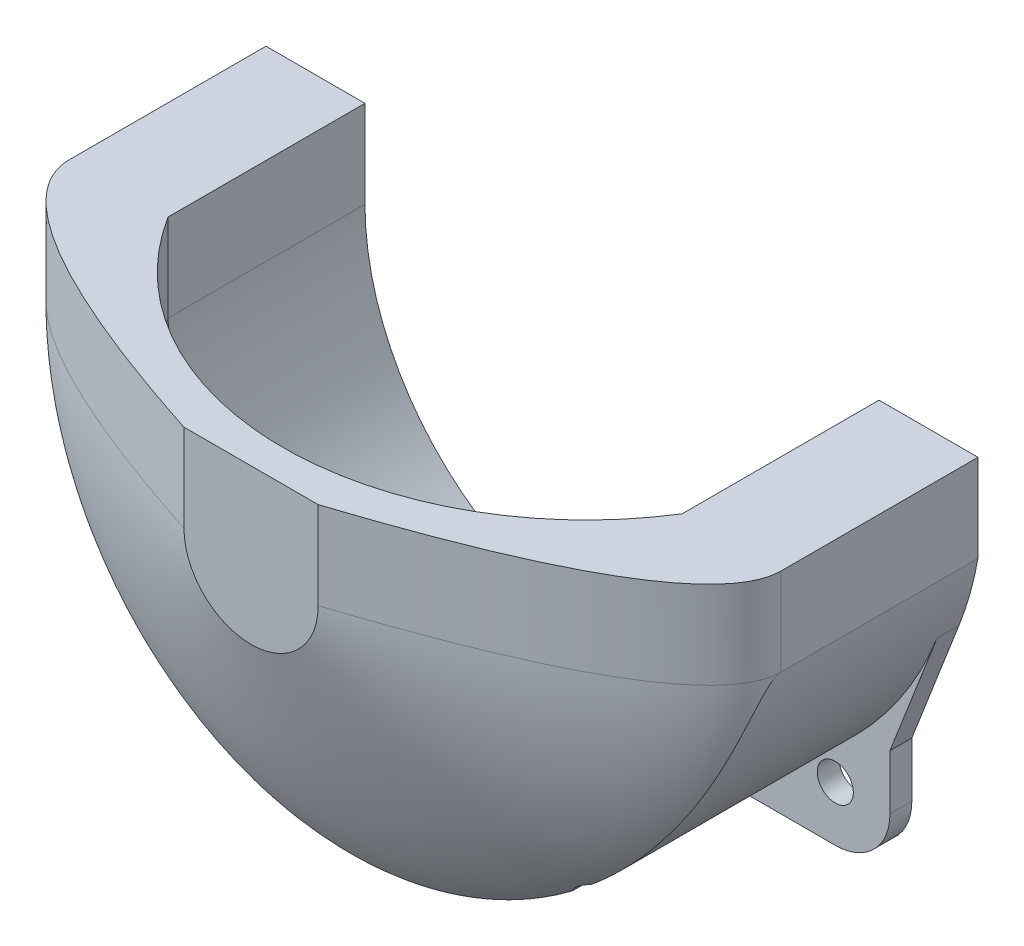
SolidWorks part; units mm, degrees
ref_plane "前视基准面" through (0, 0, 0) normal (0, 0, 1) x (1, 0, 0)
ref_plane "上视基准面" through (0, 0, 0) normal (0, 1, 0) x (1, 0, 0)
ref_plane "右视基准面" through (0, 0, 0) normal (1, 0, 0) x (0, 0, -1)
sketch "草图1" plane through (0, 0, 0) normal (0, 0, 1) x (1, 0, 0)
  line L0 (-1000, 0) -> (49000, 0)
  line L1 (-26.5, 27.25) -> (26.5, 27.25)
  line L2 (-26.5, 27.25) -> (-26.5, -27.25)
  line L3 (-26.5, -27.25) -> (26.5, -27.25)
  line L4 (26.5, 27.25) -> (26.5, -27.25)
  line L5 (-26.5, 27.25) -> (26.5, -27.25) construction
  line L6 (-26.5, -27.25) -> (26.5, 27.25) construction
  circle A0 centre (0, 0) radius 23.5
  dimension "D1" = 47
  dimension "D2" = 27.25
  dimension "D3" = 53
extrude "凸台-拉伸1" add sketch "草图1" along normal blind 2 contours A0 L0 L2 L3 L4 region at (-25, -0.5959, 0)
fillet "圆角1" radius 5 2 edges at (-26.5, -27.25, 1) (26.5, -27.25, 1)
sketch "草图2" plane through (0, 0, 2) normal (0, 0, 1) x (1, 0, 0)
  line L0 (42.3459, 23.4354) -> (26.5, -17.25) construction
  line L1 (-26.5, -17.25) -> (-42.3459, 23.4354) construction
  line L2 (33.2184, 0) -> (26.5, -17.25)
  line L3 (-26.5, -17.25) -> (-33.2184, 0)
  line L4 (-26.5, 0) -> (-33.2184, 0)
  line L5 (26.5, 0) -> (33.2184, 0)
  line L11 (-26.5, 0) -> (-26.5, -22.25)
  line L12 (-21.5, -27.25) -> (21.5, -27.25)
  line L13 (26.5, -22.25) -> (26.5, 0)
  line L14 (26.5, 0) -> (23.5, 0)
  line L15 (-23.5, 0) -> (-26.5, 0)
  line L16 (-26.5, 0) -> (-26.5, -17.25)
  line L18 (26.5, -17.25) -> (26.5, 0)
  circle A0 centre (-21.5, -22.25) radius 1.65 construction
  circle A1 centre (21.5, -22.25) radius 1.65 construction
  circle A2 centre (-21.5, -22.25) radius 1.65
  circle A3 centre (21.5, -22.25) radius 1.65
  arc A7 (-26.5, -22.25) -> (-21.5, -27.25) centre (-21.5, -22.25) ccw
  arc A8 (21.5, -27.25) -> (26.5, -22.25) centre (21.5, -22.25) ccw
  arc A9 (-23.5, 0) -> (23.5, 0) centre (0, 0) ccw
  dimension "D1" = 0
extrude "凸台-拉伸2" add sketch "草图2" against normal blind 2
extrude "切除-拉伸1" cut sketch "草图2<2>" against normal blind 2 contours A2 | A3 region at (-21.5, -22.25, 2) region at (21.5, -22.25, 2)
sketch "草图2<2>" plane through (0, 0, 2) normal (0, 0, 1) x (1, 0, 0) same geometry as "草图2"
sketch "草图5" plane through (0, 0, 2) normal (0, 0, 1) x (1, 0, 0)
  line L0 (-33.2184, 0) -> (-26.5, -17.25) construction
  line L1 (26.5, -17.25) -> (33.2184, 0) construction
  line L2 (-21.5, -27.25) -> (21.5, -27.25) construction
  line L3 (23.5, 0) -> (33.2184, 0) construction
  line L4 (-33.2184, 0) -> (-23.5, 0) construction
  line L5 (23.5, 0) -> (32.5483, 0)
  line L6 (-32.5483, 0) -> (-23.5, 0)
  arc A0 (-32.5483, 0) -> (32.5483, 0) centre (0, 5.8134) ccw
  arc A1 (-23.5, 0) -> (23.5, 0) centre (0, 0) ccw construction
  arc A2 (-23.5, 0) -> (23.5, 0) centre (0, 0) ccw
extrude "凸台-拉伸3" add sketch "草图5" along normal blind 8
ref_plane "基准面4" through (0, 0, 0) normal (0, 1, 0) x (1, 0, 0)
sketch "草图8" plane through (0, 0, 0) normal (0, 1, 0) x (1, 0, 0)
  line L0 (0, -1000) -> (0, 49000) construction
  line L1 (0, -10) -> (23.5, -19) construction
  line L2 (-23.5, -10) -> (23.5, -10) construction
  line L3 (23.5, -10) -> (23.5, 0) construction
  line L4 (32.5483, -10) -> (23.5, -10) construction
  line L5 (32.5483, -10) -> (32.5483, -2) construction
  line L6 (32.5483, -10) -> (23.5, -10)
  line L7 (0, -28) -> (0, -23)
  arc A1 (0, -23) -> (23.5, -10) centre (0, 4.7404) ccw
  spline S1 degree 3 poles (32.5483, -10) (32.5483, -19.5795) (-2.0955, -28) (0, -28) knots 0 0 0 0 1 1 1 1
  dimension "D3" = 9
  dimension "D1" = 5
  dimension "D2" = 13
revolve "旋转4" add sketch "草图8" angle 180 about L7 region at (17.7639, 0, 18.2957)
sketch "草图11" plane through (0, 0, 10) normal (0, 0, -1) x (-1, 0, 0)
  line L0 (-23.5, 0) -> (-22.7697, 0)
  line L1 (22.7697, 0) -> (23.5, 0)
  line L12 (-33.2184, 0) -> (-30.8092, -6.186)
  line L13 (-32.5483, 0) -> (-33.2184, 0)
  line L14 (-33.2184, 0) -> (-30.8092, -6.186)
  line L15 (-32.5483, 0) -> (-33.2184, 0)
  line L16 (33.2184, 0) -> (32.5483, 0)
  line L17 (30.8092, -6.186) -> (33.2184, 0)
  line L18 (33.2184, 0) -> (32.5483, 0)
  line L19 (30.8092, -6.186) -> (33.2184, 0)
  arc A2 (-32.5483, 0) -> (-30.8092, -6.186) centre (0, 5.8134) ccw
  arc A3 (-32.5483, 0) -> (-30.8092, -6.186) centre (0, 5.8134) ccw
  arc A5 (-32.5483, 0) -> (32.5483, 0) centre (0, 0) ccw
  arc A6 (-32.5483, 0) -> (32.5483, 0) centre (0, 0) ccw
  arc A7 (-32.5483, 0) -> (32.5483, 0) centre (0, 5.8134) ccw
  arc A12 (30.8092, -6.186) -> (32.5483, 0) centre (0, 5.8134) ccw
  arc A13 (30.8092, -6.186) -> (32.5483, 0) centre (0, 5.8134) ccw
  arc A14 (-32.5483, 0) -> (32.5483, 0) centre (0, 5.8134) ccw
  arc A15 (-32.5483, 0) -> (32.5483, 0) centre (0, 5.8134) ccw
  arc A16 (-32.5483, 0) -> (32.5483, 0) centre (0, 0) ccw
  arc A17 (-32.5483, 0) -> (32.5483, 0) centre (0, 5.8134) ccw
  arc A18 (-32.5483, 0) -> (32.5483, 0) centre (0, 0) ccw
  arc M21 (-32.5483, 0) -> (32.5483, 0) centre (0, 0) ccw
  arc M30 (32.5483, 0) -> (-32.5483, 0) centre (0, 5.8134) cw
  dimension "D2" = 0
  dimension "D4" = 0
  dimension "D1" = 0
  dimension "D3" = 0
extrude "切除-拉伸3" cut sketch "草图11" along normal blind 8 and the other way through all contours L19 L14 M30 M21 region at (31.7192, -4.0474, 10)
extrude "切除-拉伸4" cut sketch "草图11<3>" against normal through all both and the other way through all contours L15 L14 M21 | L19 L18 M21 | L19 M30 M21 | L14 M21 M30 region at (32.7602, -0.6105, 10) region at (32.1413, -2.2834, 10) region at (-32.7602, -0.6105, 10) region at (-32.1413, -2.2834, 10)
sketch "草图11<3>" plane through (0, 0, 10) normal (0, 0, -1) x (-1, 0, 0) same geometry as "草图11"
sketch "草图13" plane through (0, 0, 0) normal (0, 1, 0) x (1, 0, 0)
  line L6 (-23.5, 0) -> (-32.5483, 0)
  line L7 (-32.5483, 0) -> (-32.5483, -10)
  line L8 (32.5483, -10) -> (32.5483, 0)
  line L9 (32.5483, 0) -> (23.5, 0)
  line L10 (23.5, 0) -> (23.5, -10)
  line L11 (-23.5, -10) -> (-23.5, 0)
  line L12 (-23.5, 0) -> (-32.5483, 0)
  line L13 (-32.5483, 0) -> (-32.5483, -10)
  line L14 (32.5483, -10) -> (32.5483, 0)
  line L15 (32.5483, 0) -> (23.5, 0)
  line L16 (23.5, 0) -> (23.5, -10)
  line L17 (-23.5, -10) -> (-23.5, 0)
  arc A1 (-23.5, -10) -> (23.5, -10) centre (0, 4.7404) ccw
  arc A2 (-23.5, -10) -> (23.5, -10) centre (0, 4.7404) ccw
  spline S2 degree 3 poles (1966.3519, -41.5207) (-2200.839, 170.7352) (2160.848, -304.4807) (-1978.2692, 265.2006) knots -2.620825 -2.620825 -2.620825 -2.620825 3.581245 3.581245 3.581245 3.581245 only from (-32.5483, -10) to (0, -27.9126)
  spline S3 degree 3 poles (1978.2787, 265.2019) (-2160.8484, -304.4806) (2200.8291, 170.7339) (-1966.333, -41.5198) knots -2.640567 -2.640567 -2.640567 -2.640567 3.561499 3.561499 3.561499 3.561499 only from (0, -27.9126) to (32.5483, -10)
  spline S4 degree 3 poles (-32.5483, -10) (-32.5483, -19.0113) (-1.8925, -26.997) (0, -27.9126) knots 0 0 0 0 0.940683 0.940683 0.940683 0.940683
  spline S5 degree 3 poles (0, -27.9126) (1.8925, -26.997) (32.5483, -19.0113) (32.5483, -10) knots 0 0 0 0 0.940683 0.940683 0.940683 0.940683
  dimension "D1" = 0
extrude "凸台-拉伸4" add sketch "草图13" along normal blind 8
ref_plane "基准面5" through (0, 0, 27.9126) normal (0, 0, -1) x (-1, 0, 0)
sketch "草图16" plane through (0, 0, 27.9126) normal (0, 0, -1) x (-1, 0, 0)
  circle A0 centre (0, 0) radius 8.1
  dimension "D1" = 16.2
extrude "切除-拉伸15" cut sketch "草图16" along normal blind 2 and the other way through all
sketch "草图17" plane through (0, 8, 0) normal (0, 1, 0) x (1, 0, 0)
  line L0 (-6.1367, -25.9126) -> (-1.2689, -25.9126) construction
  line L1 (-1.2689, -25.9126) -> (-1.2689, -27.4649) construction
  line L2 (1.2689, -27.4649) -> (1.2689, -25.9126) construction
  line L3 (1.2689, -25.9126) -> (6.1367, -25.9126) construction
  line L4 (-6.1367, -25.9126) -> (-1.2689, -25.9126)
  line L5 (-1.2689, -25.9126) -> (-1.2689, -27.4649)
  line L6 (1.2689, -27.4649) -> (1.2689, -25.9126)
  line L7 (1.2689, -25.9126) -> (6.1367, -25.9126)
  spline S0 degree 3 poles (-989.4122, 126.0659) (1136.2734, -181.5533) (-1182.8044, 80.2068) (993.4674, 1.9001) knots -1.42228 -1.42228 -1.42228 -1.42228 3.580931 3.580931 3.580931 3.580931 only from (-1.2689, -27.4649) to (-6.1367, -25.9126) construction
  spline S1 degree 3 poles (-993.4763, 1.8998) (1182.8057, 80.2073) (-1136.2655, -181.5525) (989.3973, 126.0637) knots -2.640255 -2.640255 -2.640255 -2.640255 2.362951 2.362951 2.362951 2.362951 only from (6.1367, -25.9126) to (1.2689, -27.4649) construction
  spline S2 degree 3 poles (-1.2689, -27.4649) (-2.3716, -27.1085) (-4.0778, -26.5826) (-6.1367, -25.9126) knots 0.699251 0.699251 0.699251 0.699251 0.851241 0.851241 0.851241 0.851241
  spline S3 degree 3 poles (6.1367, -25.9126) (4.0778, -26.5826) (2.3716, -27.1085) (1.2689, -27.4649) knots 0.089442 0.089442 0.089442 0.089442 0.241432 0.241432 0.241432 0.241432
extrude "切除-拉伸16" cut sketch "草图17" against normal through all
sketch "草图18" plane through (0, 0, 2) normal (0, 0, 1) x (1, 0, 0)
  circle A0 centre (-21.5, -22.25) radius 2.5
  circle A1 centre (21.5, -22.25) radius 2.5
  dimension "D1" = 5
  dimension "D2" = 5
extrude "切除-拉伸17" cut sketch "草图18" along normal through all
sketch "草图19" plane through (0, 0, 0) normal (0, 0, -1) x (-1, 0, 0)
  line L11 (26.5, -17.25) -> (30.8092, -6.186)
  line L12 (32.5483, 0) -> (32.5483, 8)
  line L13 (32.5483, 8) -> (23.5, 8)
  line L14 (23.5, 8) -> (23.5, 0)
  line L15 (-23.5, 0) -> (-23.5, 8)
  line L16 (-23.5, 8) -> (-32.5483, 8)
  line L17 (-32.5483, 8) -> (-32.5483, 0)
  line L18 (-30.8092, -6.186) -> (-26.5, -17.25)
  line L19 (-26.5, -17.25) -> (-26.5, -22.25)
  line L20 (-21.5, -27.25) -> (21.5, -27.25)
  line L21 (26.5, -22.25) -> (26.5, -17.25)
  line L22 (26.5, -17.25) -> (30.8092, -6.186)
  line L23 (32.5483, 0) -> (32.5483, 8)
  line L24 (32.5483, 8) -> (23.5, 8)
  line L25 (23.5, 8) -> (23.5, 0)
  line L26 (-23.5, 0) -> (-23.5, 8)
  line L27 (-23.5, 8) -> (-32.5483, 8)
  line L28 (-32.5483, 8) -> (-32.5483, 0)
  line L29 (-30.8092, -6.186) -> (-26.5, -17.25)
  line L30 (-26.5, -17.25) -> (-26.5, -22.25)
  line L31 (-21.5, -27.25) -> (21.5, -27.25)
  line L32 (26.5, -22.25) -> (26.5, -17.25)
  circle A0 centre (21.5, -22.25) radius 1.65 construction
  circle A1 centre (-21.5, -22.25) radius 1.65 construction
  circle A2 centre (21.5, -22.25) radius 1.65
  circle A3 centre (-21.5, -22.25) radius 1.65
  arc A5 (30.8092, -6.186) -> (32.5483, 0) centre (0, 5.8134) ccw
  arc A6 (-23.5, 0) -> (23.5, 0) centre (0, 0) ccw
  arc A7 (-32.5483, 0) -> (-30.8092, -6.186) centre (0, 5.8134) ccw
  arc A8 (-26.5, -22.25) -> (-21.5, -27.25) centre (-21.5, -22.25) ccw
  arc A9 (21.5, -27.25) -> (26.5, -22.25) centre (21.5, -22.25) ccw
  arc A10 (30.8092, -6.186) -> (32.5483, 0) centre (0, 5.8134) ccw
  arc A11 (-23.5, 0) -> (23.5, 0) centre (0, 0) ccw
  arc A12 (-32.5483, 0) -> (-30.8092, -6.186) centre (0, 5.8134) ccw
  arc A13 (-26.5, -22.25) -> (-21.5, -27.25) centre (-21.5, -22.25) ccw
  arc A14 (21.5, -27.25) -> (26.5, -22.25) centre (21.5, -22.25) ccw
  dimension "D1" = 0
extrude "凸台-拉伸5" add sketch "草图19" along normal blind 8
sketch "草图20" plane through (0, 0, 2) normal (0, 0, 1) x (1, 0, 0)
  line L0 (0, -27.25) -> (21.5, -27.25) construction
  line L1 (26.5, -22.25) -> (26.5, -17.25) construction
  line L2 (26.5, -17.25) -> (30.8092, -6.186) construction
  line L3 (-30.8092, -6.186) -> (-26.5, -17.25) construction
  line L4 (-26.5, -17.25) -> (-26.5, -22.25) construction
  line L5 (-21.5, -27.25) -> (0, -27.25) construction
  line L6 (0, -27.25) -> (21.5, -27.25)
  line L7 (26.5, -22.25) -> (26.5, -17.25)
  line L8 (26.5, -17.25) -> (30.8092, -6.186)
  line L9 (-30.8092, -6.186) -> (-26.5, -17.25)
  line L10 (-26.5, -17.25) -> (-26.5, -22.25)
  line L11 (-21.5, -27.25) -> (0, -27.25)
  arc A0 (20.8704, -19.8306) -> (30.8092, -6.186) centre (0, 5.8134) ccw construction
  arc A1 (20.8704, -19.8306) -> (19.3278, -21.0124) centre (21.5, -22.25) ccw construction
  arc A2 (0, -27.25) -> (19.3278, -21.0124) centre (0, 5.8134) ccw construction
  arc A3 (21.5, -27.25) -> (26.5, -22.25) centre (21.5, -22.25) ccw construction
  arc A4 (-19.3278, -21.0124) -> (0, -27.25) centre (0, 5.8134) ccw construction
  arc A5 (-19.3278, -21.0124) -> (-20.8704, -19.8306) centre (-21.5, -22.25) ccw construction
  arc A6 (-30.8092, -6.186) -> (-20.8704, -19.8306) centre (0, 5.8134) ccw construction
  arc A7 (-26.5, -22.25) -> (-21.5, -27.25) centre (-21.5, -22.25) ccw construction
  arc A8 (20.8704, -19.8306) -> (30.8092, -6.186) centre (0, 5.8134) ccw
  arc A9 (20.8704, -19.8306) -> (19.3278, -21.0124) centre (21.5, -22.25) ccw
  arc A10 (0, -27.25) -> (19.3278, -21.0124) centre (0, 5.8134) ccw
  arc A11 (21.5, -27.25) -> (26.5, -22.25) centre (21.5, -22.25) ccw
  arc A12 (-19.3278, -21.0124) -> (0, -27.25) centre (0, 5.8134) ccw
  arc A13 (-19.3278, -21.0124) -> (-20.8704, -19.8306) centre (-21.5, -22.25) ccw
  arc A14 (-30.8092, -6.186) -> (-20.8704, -19.8306) centre (0, 5.8134) ccw
  arc A15 (-26.5, -22.25) -> (-21.5, -27.25) centre (-21.5, -22.25) ccw
  arc M1 (0, -27.25) -> (-19.3278, -21.0124) centre (0, 5.8134) cw
  arc M2 (-19.3278, -21.0124) -> (-20.8704, -19.8306) centre (-21.5, -22.25) ccw
  arc M3 (-20.8704, -19.8306) -> (-30.8092, -6.186) centre (0, 5.8134) cw
  line M4 (-30.8092, -6.186) -> (-26.5, -17.25)
  line M5 (-26.5, -17.25) -> (-26.5, -22.25)
  arc M6 (-26.5, -22.25) -> (-21.5, -27.25) centre (-21.5, -22.25) ccw
  line M7 (-21.5, -27.25) -> (0, -27.25)
  circle M8 centre (-21.5, -22.25) radius 1.65
extrude "切除-拉伸18" cut sketch "草图20" against normal blind 8 contours M7 M1 M2 M3 M4 M5 M6 M8 | L6 A11 L7 L8 A8 A9 A10 region at (20.2817, -22.7974, 2) region at (-10.75, -26.8768, 2)
